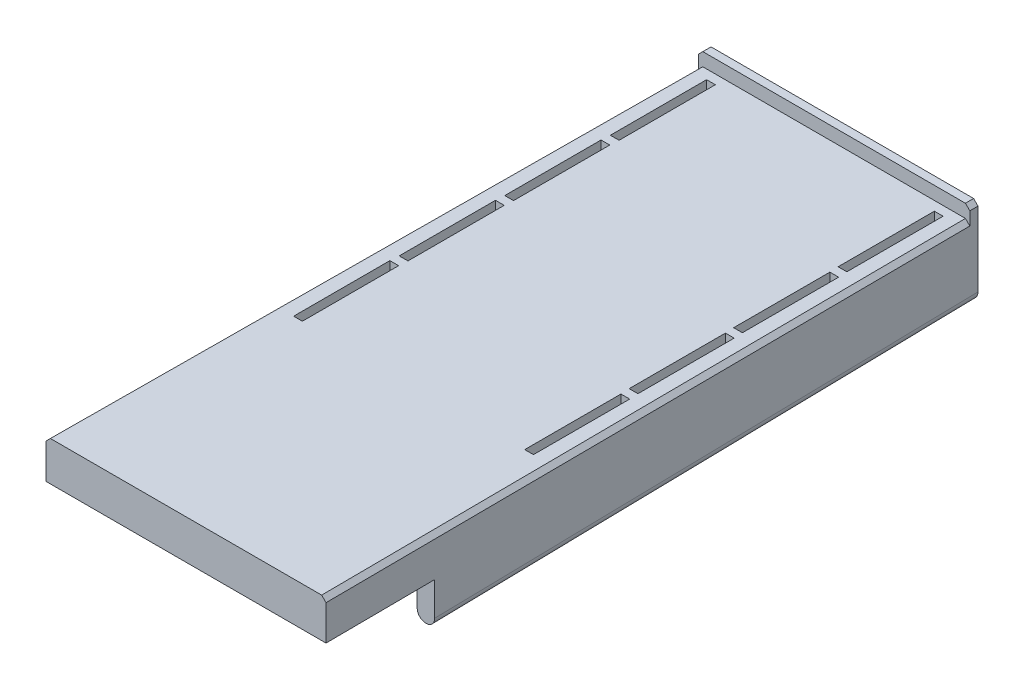
SolidWorks part; units mm, degrees
ref_plane "Front Plane" through (0, 0, 0) normal (0, 0, 1) x (1, 0, 0)
ref_plane "Top Plane" through (0, 0, 0) normal (0, 1, 0) x (1, 0, 0)
ref_plane "Right Plane" through (0, 0, 0) normal (1, 0, 0) x (0, 0, -1)
sketch "Sketch1" plane through (0, 0, 0) normal (0, 1, 0) x (1, 0, 0)
  line L0 (31, 0) -> (-31, 0)
  line L1 (0, 0) -> (0, -150) construction
  line L2 (32, -150) -> (-32, -150)
  line L3 (-32, -150) -> (-31, 0)
  line L4 (32, -150) -> (31, 0)
  dimension "\"neck length" = 150
extrude "Boss-Extrude1" add sketch "Sketch1" along normal blind 19
sketch "Sketch4" plane through (0, 0, 0) normal (1, 0, 0) x (0, 0, -1)
  line L0 (-150, 0) -> (0, 0)
  line L1 (0, 0) -> (0, 2)
  line L2 (0, 19) -> (0, 0) construction
  line L4 (0, 2) -> (-150, 0)
extrude "Cut-Extrude1" cut sketch "Sketch4" against normal through all both and the other way through all
shell "Shell1" thickness 4 removed face at (0, 1, 75)
fillet "Fillet2" 2 edges at (31.5, 1, 75) (27.4999, 1, 75) type full round first side face at (31.5, 10, 75) second side face at (27.4999, 5.5, 75) middle face at (0, 1, 75)
fillet "Fillet3" 2 edges at (-31.5, 1, 75) (-27.4999, 1, 75) type full round first side face at (-31.5, 10, 75) second side face at (-27.4999, 5.5, 75) middle face at (0.0001, 1, 75)
sketch "Sketch5" plane through (0, 19, 0) normal (0, 1, 0) x (1, 0, 0)
  line L0 (-31, 0) -> (-31.0125, -1.8797)
  line L1 (-31, 0) -> (-32, -150) construction
  line L2 (-31.0125, -1.8797) -> (31.0125, -1.8797)
  line L3 (32, -150) -> (31, 0) construction
  line L4 (31.0125, -1.8797) -> (31, 0)
  line L5 (31, 0) -> (-31, 0)
extrude "Boss-Extrude2" add sketch "Sketch5" along normal blind 3
chamfer "Chamfer1" distance 1 angle 45 2 edges at (31.5063, 19, 75.9398) (-31.5063, 19, 75.9398)
chamfer "Chamfer2" distance 1 angle 45 2 edges at (31.0063, 22, 0.9398) (-31.0063, 22, 0.9398)
sketch "Sketch6" plane through (0, 19, 0) normal (0, 1, 0) x (1, 0, 0)
  line L0 (-30.0125, -1.8797) -> (30.0125, -1.8797)
  line L1 (0, -1.8797) -> (0, -197.9912) construction
  line L2 (-31.316, -197.3975) -> (31.316, -197.3975)
  line L3 (31, -150) -> (30.0125, -1.8797) construction
  line L4 (31.316, -197.3975) -> (30.0125, -1.8797)
  line L5 (-30.0125, -1.8797) -> (-31.316, -197.3975)
  line L6 (-30.0125, -1.8797) -> (-31, -150) construction
extrude "Cut-Extrude2" [suppressed] cut sketch "Sketch6" against normal blind 1.6
sketch "Sketch7" plane through (0, 0, 150) normal (0, 0, 1) x (1, 0, 0)
  line L1 (-32, 10) -> (32, 10)
  line L2 (-32, 18) -> (-32, 2) construction
  line L3 (32, 18) -> (32, 2) construction
  line L4 (32, 10) -> (32, 0)
  line L7 (-32, 0) -> (-32, 10)
  line L8 (-32, 0) -> (32, 0)
extrude "Cut-Extrude3" cut sketch "Sketch7" against normal blind 25
sketch "Sketch8" plane through (0, 0, 1.8797) normal (0, 0, 1) x (1, 0, 0)
  line L0 (-30.0125, 19) -> (30.0125, 19) construction
  line L1 (-30.0125, 19) -> (30.0125, 19)
  spline S0 degree 2 poles (-30.0125, 19) (0, 23) (30.0125, 19) knots 0 0 0 1 1 1
  point P5 (-29.8234, 19.3133)
  point P8 (-31, 19)
  point P10 (31, 19)
  point P12 (-31, 19)
  point P13 (-30.0125, 19)
  point P15 (0, 0)
  point P16 (30.0125, 19)
  dimension "D1" = 2
sketch "Sketch9" plane through (0, 0, 150) normal (0, 0, 1) x (1, 0, 0)
  line L0 (-31, 19) -> (31, 19)
  line L1 (0, 19) -> (0, 21) construction
  spline S0 degree 2 poles (-31, 19) (0, 23) (31, 19) knots 0 0 0 1 1 1
  point P7 (-29.9656, 19.5589)
  point P8 (-31, 19)
  point P9 (30.0125, 19)
  point P12 (30.0125, 19)
  point P13 (-30.0125, 19)
  point P14 (0, 0)
  point P15 (-30.0125, 19)
  point P16 (30.0125, 19)
  point P18 (-30.0125, 19)
  point P19 (0, 0)
  point P20 (-31, 19)
sketch "Sketch11" plane through (0, 10, 0) normal (0, -1, 0) x (1, 0, 0)
  line L0 (27.1522, 27.9997) -> (27.1522, 49.9997)
  line L1 (27.0266, 4) -> (25.0266, 4)
  line L2 (27.0266, 4) -> (27.0266, 26)
  line L3 (27.0266, 26) -> (25.0266, 26)
  line L4 (25.0266, 4) -> (25.0266, 26)
  line L5 (27.1522, 27.9997) -> (25.1522, 27.9997)
  line L6 (25.1522, 27.9997) -> (25.1522, 49.9997)
  line L7 (27.1522, 49.9997) -> (25.1522, 49.9997)
  line L8 (27.2779, 51.9993) -> (27.2779, 73.9993)
  line L9 (27.2779, 51.9993) -> (25.2779, 51.9993)
  line L10 (25.2779, 51.9993) -> (25.2779, 73.9993)
  line L11 (27.2779, 73.9993) -> (25.2779, 73.9993)
  line L12 (27.4036, 75.999) -> (27.4036, 97.999)
  line L13 (27.4036, 75.999) -> (25.4036, 75.999)
  line L14 (25.4036, 75.999) -> (25.4036, 97.999)
  line L15 (27.4036, 97.999) -> (25.4036, 97.999)
  line L16 (27.0266, 4) -> (27.1522, 27.9997) construction
  line L17 (0, -11.9167) -> (0, 11.9167) construction
  line L18 (-27.4036, 75.999) -> (-25.4036, 75.999)
  line L19 (-25.4036, 75.999) -> (-25.4036, 97.999)
  line L20 (-27.4036, 97.999) -> (-25.4036, 97.999)
  line L21 (-27.4036, 75.999) -> (-27.4036, 97.999)
  line L22 (-27.2779, 51.9993) -> (-25.2779, 51.9993)
  line L23 (-25.2779, 51.9993) -> (-25.2779, 73.9993)
  line L24 (-27.2779, 73.9993) -> (-25.2779, 73.9993)
  line L25 (-27.2779, 51.9993) -> (-27.2779, 73.9993)
  line L26 (-27.1522, 27.9997) -> (-25.1522, 27.9997)
  line L27 (-25.1522, 27.9997) -> (-25.1522, 49.9997)
  line L28 (-27.1522, 49.9997) -> (-25.1522, 49.9997)
  line L29 (-27.1522, 27.9997) -> (-27.1522, 49.9997)
  line L30 (-27.0266, 26) -> (-25.0266, 26)
  line L31 (-25.0266, 4) -> (-25.0266, 26)
  line L32 (-27.0266, 4) -> (-25.0266, 4)
  line L33 (-27.0266, 4) -> (-27.0266, 26)
  dimension "D1" = 22
  dimension "D2" = 2
  dimension "D4" = 24
  dimension "D3" = 4
extrude "Cut-Extrude4" cut sketch "Sketch11" against normal through all
equation "\"neck length\"= 200mm"
